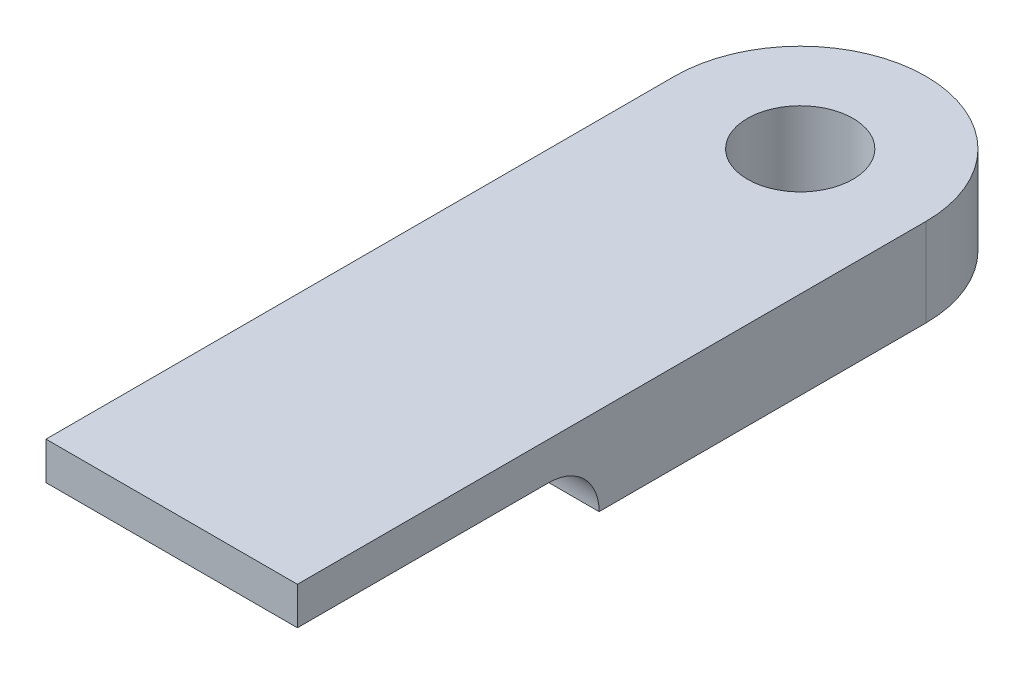
SolidWorks part; units mm, degrees
ref_plane "Alzado" through (0, 0, 0) normal (0, 0, 1) x (1, 0, 0)
ref_plane "Planta" through (0, 0, 0) normal (0, 1, 0) x (1, 0, 0)
ref_plane "Vista lateral" through (0, 0, 0) normal (1, 0, 0) x (0, 0, -1)
sketch "Croquis1" plane through (0, 0, 0) normal (0, 1, 0) x (1, 0, 0)
  line L1 (5, -15) -> (-5, -15)
  line L2 (5, -15) -> (5, 15)
  line L3 (5, 15) -> (-5, 15)
  line L4 (-5, -15) -> (-5, 15)
  line L5 (5, -15) -> (-5, 15) construction
  line L6 (5, 15) -> (-5, -15) construction
  point P0 (0, 0)
  dimension "D1" = 10
  dimension "D2" = 30
extrude "Saliente-Extruir1" add sketch "Croquis1" along normal mid plane 3.5
fillet "Redondeo1" radius 5 2 edges at (5, 0, -15) (-5, 0, -15)
sketch "Croquis2" plane through (0, 1.75, 0) normal (0, 1, 0) x (1, 0, 0)
  circle A0 centre (0, 10) radius 2.1
  dimension "D1" = 4.2
extrude "Cortar-Extruir1" cut sketch "Croquis2" against normal blind 3.5
sketch "Croquis3" plane through (0, -1.75, 0) normal (0, -1, 0) x (1, 0, 0)
  line L0 (5, 15) -> (5, -10) construction
  line L1 (-5, 15) -> (5, 15)
  line L2 (-5, 15) -> (-5, 3)
  line L3 (-5, 3) -> (5, 3)
  line L4 (5, 15) -> (5, 3)
  dimension "D1" = 12
extrude "Cortar-Extruir2" cut sketch "Croquis3" against normal blind 2
fillet "Redondeo2" radius 2 1 edges at (0, 0.25, 3)
